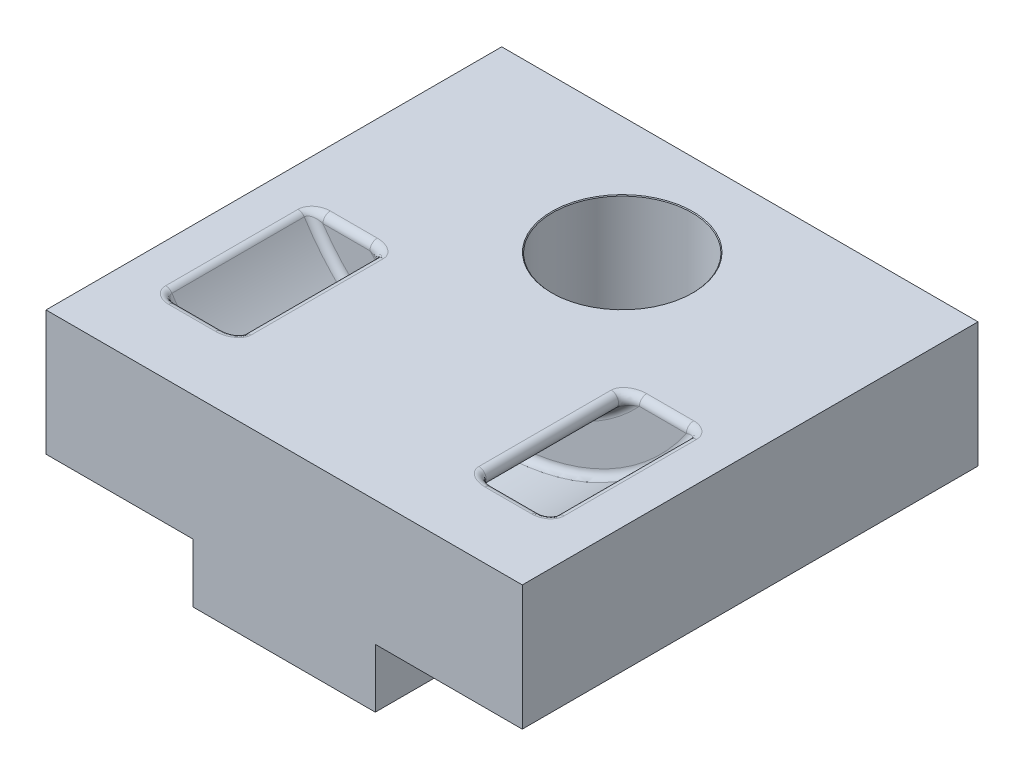
SolidWorks part; units mm, degrees
ref_plane "Front Plane" through (0, 0, 0) normal (0, 0, 1) x (1, 0, 0)
ref_plane "Top Plane" through (0, 0, 0) normal (0, 1, 0) x (1, 0, 0)
ref_plane "Right Plane" through (0, 0, 0) normal (1, 0, 0) x (0, 0, -1)
sketch "Sketch1" plane through (0, 0, 0) normal (0, 0, 1) x (1, 0, 0)
  line L0 (-3.1, 1) -> (-8.1, 1)
  line L2 (-3.1, 1) -> (-3.1, -1)
  line L3 (-3.1, -1) -> (3.1, -1)
  line L4 (3.1, 1) -> (3.1, -1)
  line L5 (-3.1, 1) -> (3.1, -1) construction
  line L6 (-3.1, -1) -> (3.1, 1) construction
  line L7 (-8.1, 1) -> (-8.1, 5.25)
  line L8 (3.1, 1) -> (8.1, 1)
  line L9 (8.1, 1) -> (8.1, 5.25)
  line L10 (8.1, 5.25) -> (6.638, 5.25)
  line L11 (0, 5.25) -> (0, 9.25)
  line L12 (-6.638, 5.25) -> (-8.1, 5.25)
  line L13 (4.4721, 5.25) -> (-4.4721, 5.25)
  arc A0 (-4.4721, 5.25) -> (4.4721, 5.25) centre (0, 9.25) ccw
  arc A1 (-6.638, 5.25) -> (6.638, 5.25) centre (0, 9.25) ccw
  point P0 (0, 0)
  dimension "D7" = 12
  dimension "D8" = 1.75
  dimension "D1" = 2
  dimension "D2" = 6.2
  dimension "D3" = 5
  dimension "D4" = 4.25
  dimension "D5" = 5
  dimension "D6" = 4
  dimension "D9" = 2
extrude "Boss-Extrude1" add sketch "Sketch1" along normal blind 5 contours L13 A0 | A1 L12 L7 L0 L2 L3 L4 L8 L9 L10 region at (-5.6, 1.1736, 0) region at (0, 4.4373, 0)
sketch "Sketch2" plane through (0, 0, 5) normal (0, 0, 1) x (1, 0, 0)
  line L0 (3.1, 1) -> (8.1, 1)
  line L1 (-8.1, 5.25) -> (8.1, 5.25)
  line L2 (-8.1, 5.25) -> (-8.1, 1)
  line L3 (-8.1, 1) -> (-3.1, 1)
  line L4 (8.1, 5.25) -> (8.1, 1)
  line L6 (-3.1, 1) -> (-3.1, -1)
  line L7 (-3.1, -1) -> (3.1, -1)
  line L8 (3.1, 1) -> (3.1, -1)
extrude "Boss-Extrude2" add sketch "Sketch2" along normal blind 2.5
sketch "Sketch3" plane through (0, 0, 0) normal (0, 0, -1) x (-1, 0, 0)
  line L0 (3.1, 1) -> (8.1, 1)
  line L1 (-8.1, 5.25) -> (8.1, 5.25)
  line L2 (-8.1, 5.25) -> (-8.1, 1)
  line L3 (-8.1, 1) -> (-3.1, 1)
  line L4 (8.1, 5.25) -> (8.1, 1)
  line L6 (-3.1, 1) -> (-3.1, -1)
  line L7 (-3.1, -1) -> (3.1, -1)
  line L8 (3.1, 1) -> (3.1, -1)
extrude "Boss-Extrude3" add sketch "Sketch3" along normal blind 8
sketch "Sketch4" plane through (0, 5.25, 0) normal (0, 1, 0) x (1, 0, 0)
  line L0 (-8.1, 8) -> (8.1, 8) construction
  point P0 (0, 4)
  dimension "D1" = 4
hole_wizard "Ø4.0mm Dowel Hole1" positions "Sketch4" profile "Sketch6" hole size "Ø4.0" standard "ANSI Metric" end condition through all
sketch "Sketch6" plane through (0, 5.25, -4) normal (1, 0, 0) x (0, 0, 1)
  line L0 (0, 0) -> (0, 6.25)
  line L1 (0, 6.25) -> (2.375, 6.25)
  line L2 (2.375, 6.25) -> (2.375, 0.025)
  line L3 (2.375, 0.025) -> (2.4, 0)
  line L5 (2.4, 0) -> (0, 0)
  line L6 (-2.375, 0.025) -> (-2.4, 0) construction
  line L11 (0, -6.35) -> (0, 107.95) construction
  dimension "Thru Hole Dia." = 4.75
  dimension "Thru Hole Depth" = 6.25
  dimension "Near C'Sink Dia." = 4.8
  dimension "Near C'Sink Angle" = 90
fillet "Fillet2" radius 0.25 12 edges at (4.4721, 5.25, 2.5) (-4.4721, 5.25, 2.5) (0, 1.5, 5) (0, 1.5, 0) (5.555, 5.25, 5) (5.555, 5.25, 0) (-5.555, 5.25, 5) (-5.555, 5.25, 0) (6.638, 5.25, 2.5) (-6.638, 5.25, 2.5) (0, 3.25, 0) (0, 3.25, 5)
